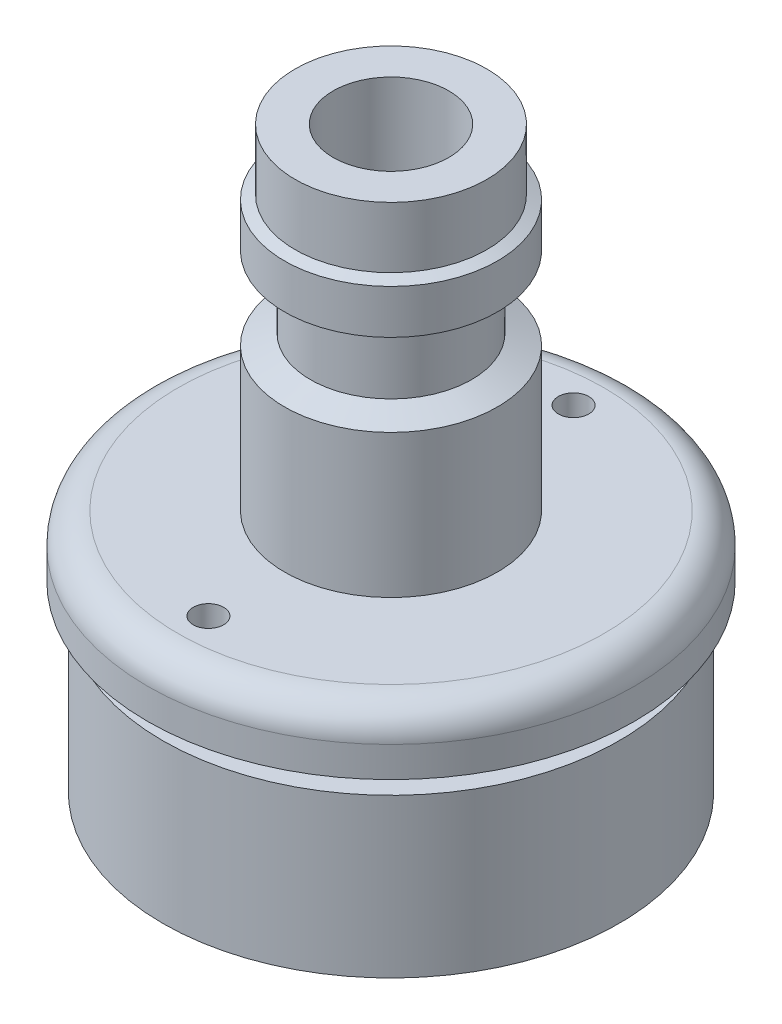
SolidWorks part; units mm, degrees
extrude "Shaft" add sketch "Sketch1" against normal blind 7.62
sketch "Sketch1" plane through (0, 0, 0) normal (0, 1, 0) x (1, 0, 0)
  circle A0 centre (0, 0) radius 9.525
  dimension "D1" = 19.05
material "PW20:22:Sc:0:"
ref_plane "Plane1" through (0, 0, 0) normal (0, 0, 1) x (1, 0, 0)
ref_plane "Plane2" through (0, 0, 0) normal (0, 1, 0) x (1, 0, 0)
ref_plane "Plane3" through (0, 0, 0) normal (1, 0, 0) x (0, 0, -1)
ref_plane "Thread Start" through (0, 1.5875, 0) normal (0, 1, 0) x (-1, 0, 0)
sketch "Sketch5" plane through (0, 1.5875, 0) normal (0, 1, 0) x (-1, 0, 0)
  circle A0 centre (0, 0) radius 9.525 construction
  circle A1 centre (0, 0) radius 9.525
curve "Helix2" pitch 1.5875 height 9.525 turns 6
sketch "Sketch6" plane through (0, 0, 0) normal (1, 0, 0) x (0, 0, -1)
  line L0 (-9.6109, 1.5379) -> (-8.4939, 0.893)
  line L1 (-8.4939, 0.893) -> (-8.4939, 0.6945)
  line L2 (-8.4939, 0.6945) -> (-9.6109, 0.0496)
  line L3 (-9.6109, 0.0496) -> (-9.6109, 1.5379)
  line L4 (-8.322, 0.7937) -> (-13.2352, 0.7937) construction
  line L5 (21.8496, 1.5875) -> (-21.8496, 1.5875) construction
  point P6 (-9.525, 0)
  point P10 (-9.525, 1.4883)
  dimension "D1" = 60
  dimension "RootWidth" = 0.1984
  dimension "HalfPitch" = 0.7937
sweep "Thread" [suppressed] cut profiles "Sketch6" path "Helix2"
sketch "Sketch10" plane through (0, 0, 0) normal (1, 0, 0) x (0, 0, -1)
  line L0 (-9.6109, -0.0496) -> (-8.4939, -0.6945)
  line L1 (-8.4939, -0.6945) -> (-8.4939, -0.893)
  line L2 (-8.4939, -0.893) -> (-9.6109, -1.5379)
  line L3 (-9.6109, -1.5379) -> (-9.6109, -0.0496)
  line L4 (-8.322, -0.7937) -> (-10.8476, -0.7937) construction
  line L5 (0, 0) -> (0, -7.3295) construction
  point P6 (-9.525, 0)
  point P10 (-9.525, -0.0992)
  dimension "D1" = 60
  dimension "RootWidth" = 0.1984
  dimension "HalfPitch" = 0.7937
  dimension "D2" = 0.6945
revolve "Simple Thread" [suppressed] cut sketch "Sketch10" angle 360 about L5
pattern_linear "Pattern Simple Thread" [suppressed] count 5 spacing 1.5875
sketch "Sketch11" plane through (0, 0, 0) normal (0, 1, 0) x (1, 0, 0)
  line L0 (-3.8123, 9.779) -> (3.4849, 9.779) construction
  circle A0 centre (0, 0) radius 8.509
  circle A1 centre (0, 0) radius 9.779
  circle A2 centre (0, 0) radius 9.525 construction
  dimension "D2" = 17.018
  dimension "D1" = 0.254
extrude "Thread Recess" cut sketch "Sketch11" against normal blind 1.016
sketch "Sketch12" plane through (0, 0, 0) normal (0, 0, 1) x (1, 0, 0)
  line L0 (0, 0) -> (0, 23.1285) construction
  line L1 (0, 0) -> (10.16, 0)
  line L2 (10.16, 0) -> (10.16, 1.27)
  line L3 (8.89, 2.54) -> (4.445, 2.54)
  line L4 (4.445, 2.54) -> (4.445, 8.509)
  line L5 (4.445, 13.7859) -> (4.0005, 13.97)
  line L6 (4.0005, 13.97) -> (4.0005, 16.51)
  line L7 (4.0005, 16.51) -> (0, 16.51)
  line L8 (0, 16.51) -> (0, 0)
  line L9 (4.445, 11.9433) -> (3.3655, 11.4961)
  line L10 (3.3655, 11.4961) -> (3.3655, 8.9561)
  line L11 (3.3655, 8.9561) -> (4.445, 8.509)
  line L12 (4.445, 11.9433) -> (4.445, 13.7859)
  line L13 (3.3655, 10.2261) -> (6.1245, 10.2261) construction
  arc A0 (10.16, 1.27) -> (8.89, 2.54) centre (8.89, 1.27) ccw
  dimension "D6" = 1.27
  dimension "D1" = 10.16
  dimension "D2" = 4.445
  dimension "D3" = 3.3655
  dimension "D4" = 4.0005
  dimension "D5" = 45
  dimension "D7" = 2.54
  dimension "D8" = 5.969
  dimension "D9" = 2.54
  dimension "D10" = 13.97
  dimension "D11" = 2.54
revolve "Standard Connector" add sketch "Sketch12" angle 360 about L0
sketch "Sketch13" plane through (0, 0, 0) normal (0, 1, 0) x (1, 0, 0)
  circle A0 centre (0, 0) radius 7.1374
  dimension "D1" = 14.2748
extrude "Large Hole" cut sketch "Sketch13" against normal through all
sketch "Sketch14" plane through (0, 0, 0) normal (0, 1, 0) x (1, 0, 0)
  circle A0 centre (0, 0) radius 2.413
  dimension "D1" = 4.826
extrude "Small Hole" cut sketch "Sketch14" along normal through all
chamfer "Chamfer1" distance 1.778 angle 45 1 edges at (0, 0, 2.413)
fillet "Fillet1" [suppressed] radius 0.254
chamfer "Chamfer2" [suppressed] distance 0.254 angle 45
chamfer "Chamfer3" [suppressed] distance 0.254 angle 45
sketch "Sketch15" plane through (0, 2.54, 0) normal (0, 1, 0) x (-1, 0, 0)
  line L0 (0, 0) -> (-6.4425, 0) construction
  line L1 (0, 50) -> (0, -50) construction
  circle A0 centre (0, -7.62) radius 0.635
  circle A1 centre (0, 7.62) radius 0.635
  dimension "D2" = 1.27
  dimension "D1" = 7.62
extrude "Tool Holes" cut sketch "Sketch15" against normal blind 1.524
chamfer "Chamfer4" [suppressed] distance 0.127 angle 45
equation "\"HalfPitch@Sketch6\" = \"Pitch@Thread Start\" / 2"
equation "\"RootWidth@Sketch6\" = \"Pitch@Thread Start\" / 8"
equation "\"ODThickness@Sketch6\" = \"RootWidth@Sketch6\" / 2"
equation "\"D5@Sketch6\" = \"ODThickness@Sketch6\" / 2"
equation "\"HalfPitch@Sketch10\" = \"HalfPitch@Sketch6\""
equation "\"RootWidth@Sketch10\" = \"RootWidth@Sketch6\""
equation "\"D3@Pattern Simple Thread\" = \"Pitch@Thread Start\""
equation "\"D2@Sketch10\" = \"HalfPitch@Sketch10\" - \"RootWidth@Sketch10\" / 2"
equation "\"D7@Sketch10\" = \"D5@Sketch6\""
